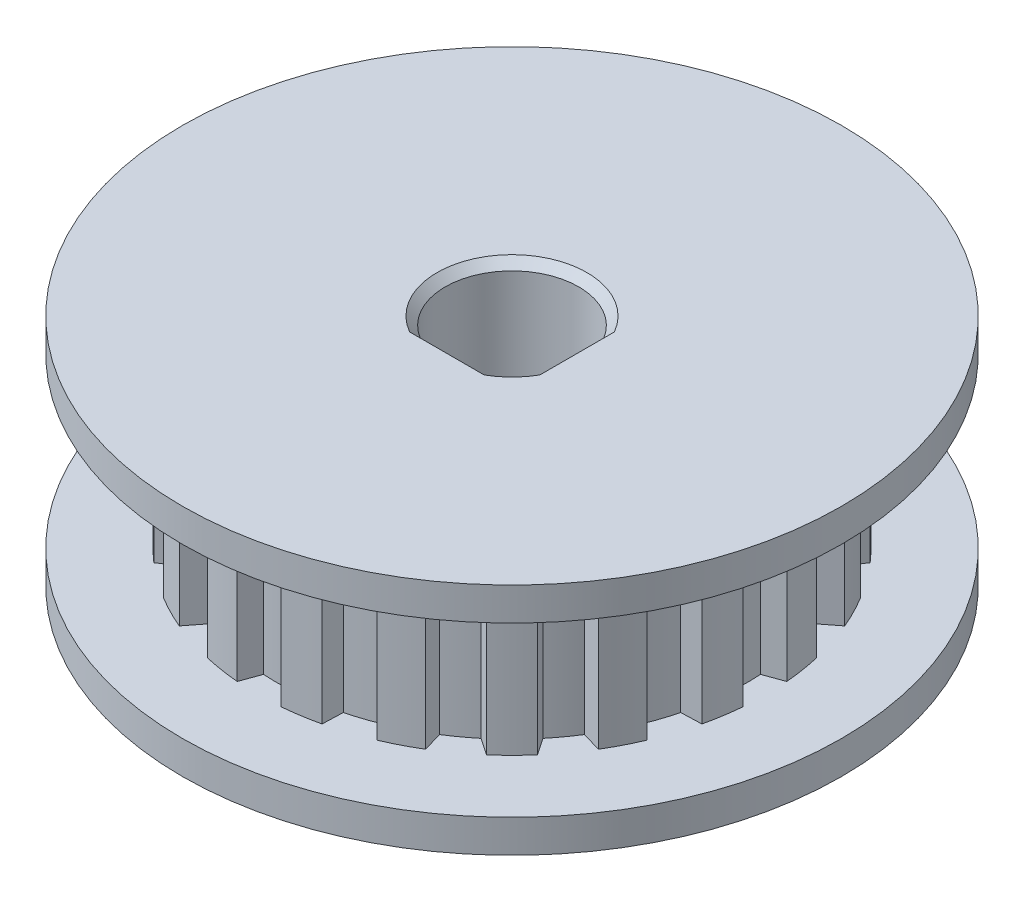
SolidWorks part; units mm, degrees
ref_plane "Спереди" through (0, 0, 0) normal (0, 0, 1) x (1, 0, 0)
ref_plane "Сверху" through (0, 0, 0) normal (0, 1, 0) x (1, 0, 0)
ref_plane "Справа" through (0, 0, 0) normal (1, 0, 0) x (0, 0, -1)
sketch "Эскиз2" plane through (0, 0, 0) normal (0, 1, 0) x (1, 0, 0)
  line L0 (0, 0) -> (0, 16.4) construction
  line L1 (0, 0) -> (2.5655, 16.1981) construction
  line L2 (0, 0) -> (-2.5655, 16.1981) construction
  line L3 (-0.9, 14.1715) -> (-1.3263, 15.3428)
  line L4 (0.9, 14.1715) -> (1.3263, 15.3428)
  line L5 (3.5233, 13.756) -> (3.4798, 15.0017)
  line L6 (5.2352, 13.1997) -> (6.0026, 14.182)
  line L7 (7.6017, 11.994) -> (7.9452, 13.1922)
  line L8 (9.0579, 10.9359) -> (10.0913, 11.633)
  line L9 (10.9359, 9.0579) -> (11.633, 10.0913)
  line L10 (11.994, 7.6017) -> (13.1922, 7.9452)
  line L11 (13.1997, 5.2352) -> (14.182, 6.0026)
  line L12 (13.756, 3.5233) -> (15.0017, 3.4798)
  line L13 (14.1715, 0.9) -> (15.3428, 1.3263)
  line L14 (14.1715, -0.9) -> (15.3428, -1.3263)
  line L15 (13.756, -3.5233) -> (15.0017, -3.4798)
  line L16 (13.1997, -5.2352) -> (14.182, -6.0026)
  line L17 (11.994, -7.6017) -> (13.1922, -7.9452)
  line L18 (10.9359, -9.0579) -> (11.633, -10.0913)
  line L19 (9.0579, -10.9359) -> (10.0913, -11.633)
  line L20 (7.6017, -11.994) -> (7.9452, -13.1922)
  line L21 (5.2352, -13.1997) -> (6.0026, -14.182)
  line L22 (3.5233, -13.756) -> (3.4798, -15.0017)
  line L23 (0.9, -14.1715) -> (1.3263, -15.3428)
  line L24 (-0.9, -14.1715) -> (-1.3263, -15.3428)
  line L25 (-3.5233, -13.756) -> (-3.4798, -15.0017)
  line L26 (-5.2352, -13.1997) -> (-6.0026, -14.182)
  line L27 (-7.6017, -11.994) -> (-7.9452, -13.1922)
  line L28 (-9.0579, -10.9359) -> (-10.0913, -11.633)
  line L29 (-10.9359, -9.0579) -> (-11.633, -10.0913)
  line L30 (-11.994, -7.6017) -> (-13.1922, -7.9452)
  line L31 (-13.1997, -5.2352) -> (-14.182, -6.0026)
  line L32 (-13.756, -3.5233) -> (-15.0017, -3.4798)
  line L33 (-14.1715, -0.9) -> (-15.3428, -1.3263)
  line L34 (-14.1715, 0.9) -> (-15.3428, 1.3263)
  line L35 (-13.756, 3.5233) -> (-15.0017, 3.4798)
  line L36 (-13.1997, 5.2352) -> (-14.182, 6.0026)
  line L37 (-11.994, 7.6017) -> (-13.1922, 7.9452)
  line L38 (-10.9359, 9.0579) -> (-11.633, 10.0913)
  line L39 (-9.0579, 10.9359) -> (-10.0913, 11.633)
  line L40 (-7.6017, 11.994) -> (-7.9452, 13.1922)
  line L41 (-5.2352, 13.1997) -> (-6.0026, 14.182)
  line L42 (-3.5233, 13.756) -> (-3.4798, 15.0017)
  circle A0 centre (0, 0) radius 16.4 construction
  circle A1 centre (0, 0) radius 15.9 construction
  circle A2 centre (0, 0) radius 15.4 construction
  circle A3 centre (0, 0) radius 14.2 construction
  arc A4 (-0.9, 14.1715) -> (0.9, 14.1715) centre (0, 0) cw
  arc A5 (3.5233, 13.756) -> (5.2352, 13.1997) centre (0, 0) cw
  arc A6 (7.6017, 11.994) -> (9.0579, 10.9359) centre (0, 0) cw
  arc A7 (10.9359, 9.0579) -> (11.994, 7.6017) centre (0, 0) cw
  arc A8 (13.1997, 5.2352) -> (13.756, 3.5233) centre (0, 0) cw
  arc A9 (14.1715, 0.9) -> (14.1715, -0.9) centre (0, 0) cw
  arc A10 (13.756, -3.5233) -> (13.1997, -5.2352) centre (0, 0) cw
  arc A11 (11.994, -7.6017) -> (10.9359, -9.0579) centre (0, 0) cw
  arc A12 (9.0579, -10.9359) -> (7.6017, -11.994) centre (0, 0) cw
  arc A13 (5.2352, -13.1997) -> (3.5233, -13.756) centre (0, 0) cw
  arc A14 (0.9, -14.1715) -> (-0.9, -14.1715) centre (0, 0) cw
  arc A15 (-3.5233, -13.756) -> (-5.2352, -13.1997) centre (0, 0) cw
  arc A16 (-7.6017, -11.994) -> (-9.0579, -10.9359) centre (0, 0) cw
  arc A17 (-10.9359, -9.0579) -> (-11.994, -7.6017) centre (0, 0) cw
  arc A18 (-13.1997, -5.2352) -> (-13.756, -3.5233) centre (0, 0) cw
  arc A19 (-14.1715, -0.9) -> (-14.1715, 0.9) centre (0, 0) cw
  arc A20 (-13.756, 3.5233) -> (-13.1997, 5.2352) centre (0, 0) cw
  arc A21 (-11.994, 7.6017) -> (-10.9359, 9.0579) centre (0, 0) cw
  arc A22 (-9.0579, 10.9359) -> (-7.6017, 11.994) centre (0, 0) cw
  arc A23 (-5.2352, 13.1997) -> (-3.5233, 13.756) centre (0, 0) cw
  arc A24 (-3.4798, 15.0017) -> (-1.3263, 15.3428) centre (0, 0) cw
  arc A25 (1.3263, 15.3428) -> (3.4798, 15.0017) centre (0, 0) cw
  arc A26 (6.0026, 14.182) -> (7.9452, 13.1922) centre (0, 0) cw
  arc A27 (10.0913, 11.633) -> (11.633, 10.0913) centre (0, 0) cw
  arc A28 (13.1922, 7.9452) -> (14.182, 6.0026) centre (0, 0) cw
  arc A29 (15.0017, 3.4798) -> (15.3428, 1.3263) centre (0, 0) cw
  arc A30 (15.3428, -1.3263) -> (15.0017, -3.4798) centre (0, 0) cw
  arc A31 (14.182, -6.0026) -> (13.1922, -7.9452) centre (0, 0) cw
  arc A32 (11.633, -10.0913) -> (10.0913, -11.633) centre (0, 0) cw
  arc A33 (7.9452, -13.1922) -> (6.0026, -14.182) centre (0, 0) cw
  arc A34 (3.4798, -15.0017) -> (1.3263, -15.3428) centre (0, 0) cw
  arc A35 (-1.3263, -15.3428) -> (-3.4798, -15.0017) centre (0, 0) cw
  arc A36 (-6.0026, -14.182) -> (-7.9452, -13.1922) centre (0, 0) cw
  arc A37 (-10.0913, -11.633) -> (-11.633, -10.0913) centre (0, 0) cw
  arc A38 (-13.1922, -7.9452) -> (-14.182, -6.0026) centre (0, 0) cw
  arc A39 (-15.0017, -3.4798) -> (-15.3428, -1.3263) centre (0, 0) cw
  arc A40 (-15.3428, 1.3263) -> (-15.0017, 3.4798) centre (0, 0) cw
  arc A41 (-14.182, 6.0026) -> (-13.1922, 7.9452) centre (0, 0) cw
  arc A42 (-11.633, 10.0913) -> (-10.0913, 11.633) centre (0, 0) cw
  arc A43 (-7.9452, 13.1922) -> (-6.0026, 14.182) centre (0, 0) cw
  point P11 (0, 14.2)
  dimension "D1" = 32.8
  dimension "D2" = 31.8
  dimension "D3" = 30.8
  dimension "D4" = 28.4
  dimension "D7" = 1.8
  dimension "D5" = 9
  dimension "D6" = 9
  dimension "D8" = 20
  dimension "D9" = 20
extrude "Вытянуть1" add sketch "Эскиз2" along normal blind 10.2
sketch "Эскиз3" plane through (0, 10.2, 0) normal (0, 1, 0) x (1, 0, 0)
  circle A0 centre (0, 0) radius 20
  dimension "D1" = 40
extrude "Вытянуть2" add sketch "Эскиз3" along normal blind 2
sketch "Эскиз4" plane through (0, 0, 0) normal (0, -1, 0) x (1, 0, 0)
  circle A0 centre (0, 0) radius 20
  circle A1 centre (0, 0) radius 20 construction
extrude "Вытянуть3" add sketch "Эскиз4" along normal blind 2
sketch "Эскиз5" plane through (0, 12.2, 0) normal (0, 1, 0) x (1, 0, 0)
  line L0 (3.45, -2.1213) -> (3.45, 2.1213)
  line L1 (2.1213, -3.45) -> (-2.1213, -3.45)
  circle A0 centre (0, 0) radius 4.05 construction
  arc A1 (2.1213, -3.45) -> (3.45, -2.1213) centre (0, 0) ccw
  arc A2 (-2.1213, -3.45) -> (3.45, 2.1213) centre (0, 0) cw
  dimension "D1" = 8.1
  dimension "D2" = 3.45
  dimension "D3" = 3.45
extrude "Вытянуть4" cut sketch "Эскиз5" against normal blind 10
sketch "Эскиз6" plane through (0, -2, 0) normal (0, -1, 0) x (1, 0, 0)
  circle A0 centre (0, 0) radius 4.05
  dimension "D1" = 8.1
extrude "Вытянуть5" cut sketch "Эскиз6" against normal up to surface (4.2 mm away) up to face at (0.8625, 2.2, 0.8625)
chamfer "Фаска1" distance 0.5 angle 45 4 edges at (3.45, 12.2, 0) (2.8638, 12.2, 2.8638) (0, 12.2, 3.45) (-2.8638, 12.2, -2.8638)
chamfer "Фаска2" distance 0.5 angle 45 1 edges at (0, -2, -4.05)
